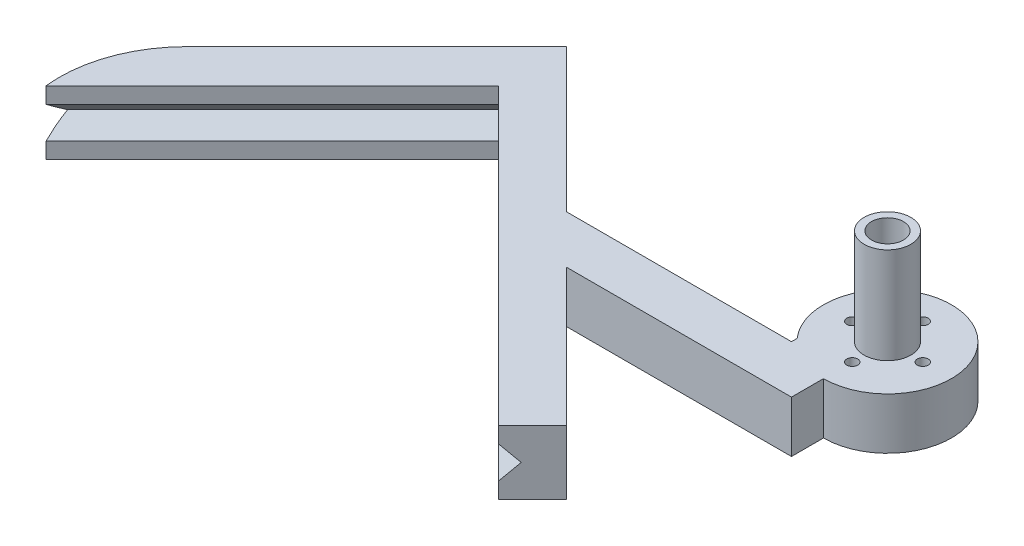
SolidWorks part; units mm, degrees
ref_plane "Front Plane" through (0, 0, 0) normal (0, 0, 1) x (1, 0, 0)
ref_plane "Top Plane" through (0, 0, 0) normal (0, 1, 0) x (1, 0, 0)
ref_plane "Right Plane" through (0, 0, 0) normal (1, 0, 0) x (0, 0, -1)
sketch "Sketch1" plane through (0, 0, 0) normal (0, 1, 0) x (1, 0, 0)
  circle A3 centre (0, -38.254) radius 38.254 construction
  circle A4 centre (0, -40.254) radius 40.254 construction
  circle A5 centre (0, -45.254) radius 45.254 construction
  dimension "D1" = 90.508
  dimension "D2" = 80.508
  dimension "D3" = 76.508
sketch "Sketch3" plane through (0, 0, 0) normal (0, 1, 0) x (1, 0, 0)
  line L8 (58.3717, -39.6268) -> (0, 18.7448)
  line L9 (0, 18.7448) -> (-58.3717, -39.6268)
  line L10 (-58.3717, -39.6268) -> (58.3717, -39.6268) construction
  line L17 (65.1069, -32.8917) -> (37.9076, -5.6924)
  line L18 (0, 32.2152) -> (-65.1069, -32.8917)
  line L19 (-65.1069, -32.8917) -> (-58.3717, -39.6268)
  line L20 (65.1069, -32.8917) -> (58.3717, -39.6268)
  line L23 (82.55, 3.8326) -> (82.55, -5.6924)
  line L26 (65.1069, -32.8917) -> (0, 32.2152) construction
  line L27 (0, 32.2152) -> (-65.1069, -32.8917) construction
  line L28 (28.3826, 3.8326) -> (73.025, 3.8326)
  line L29 (82.55, -5.6924) -> (37.9076, -5.6924)
  line L30 (28.3826, 3.8326) -> (0, 32.2152)
  line L31 (82.55, 3.8326) -> (82.55, 13.3576)
  line L32 (82.55, 13.3576) -> (73.025, 13.3576)
  line L33 (73.025, 13.3576) -> (73.025, 3.8326)
  circle A3 centre (0, -45.254) radius 45.254 construction
  dimension "D1" = 45
  dimension "D2" = 45
  dimension "D3" = 82.55
  dimension "D5" = 9.525
  dimension "D7" = 82.55
  dimension "D6" = 9.525
  dimension "D8" = 52.9844
  dimension "D9" = 9.525
  dimension "D4" = 9.525
extrude "Boss-Extrude1" add sketch "Sketch3" along normal blind 19.05
sketch "Sketch11" plane through (0, 0, 0) normal (0, 1, 0) x (1, 0, 0)
  circle A0 centre (82.55, 13.3576) radius 12.7
  dimension "D1" = 25.4
extrude "Boss-Extrude2" add sketch "Sketch11" along normal blind 19.05
sketch "Sketch14" plane through (0, 0, 0) normal (0, -1, 0) x (1, 0, 0)
  circle A0 centre (89.55, -13.3576) radius 1.077
  circle A2 centre (82.55, -20.3576) radius 1.077
  circle A3 centre (75.55, -13.3576) radius 1.077
  circle A4 centre (82.55, -6.3576) radius 1.077
  circle A5 centre (82.55, -13.3576) radius 12.7 construction
  point P17 (82.55, -13.3576)
  dimension "D2" = 2.154
  dimension "D1" = 7
  dimension "D3" = 4
extrude "Cut-Extrude4" cut sketch "Sketch14" against normal through all
sketch "Sketch16" plane through (0, 0, 0) normal (0, -1, 0) x (1, 0, 0)
  line L2 (37.9076, 5.6924) -> (28.3826, -3.8326)
  line L7 (-65.1069, 32.8917) -> (0, -32.2152)
  line L8 (65.1069, 32.8917) -> (58.3717, 39.6268)
  line L9 (58.3717, 39.6268) -> (0, -18.7448)
  line L10 (0, -18.7448) -> (-58.3717, 39.6268)
  line L20 (-58.3717, 39.6268) -> (-65.1069, 32.8917)
  line L24 (28.3826, -3.8326) -> (73.025, -3.8326)
  line L30 (37.9076, 5.6924) -> (65.1069, 32.8917)
  line L35 (28.3826, -3.8326) -> (73.025, -3.8326)
  line L37 (82.55, 5.6924) -> (37.9076, 5.6924)
  line L38 (82.55, 5.6924) -> (37.9076, 5.6924)
  line L40 (0, -32.2152) -> (28.3826, -3.8326)
  line L47 (82.55, -0.6576) -> (82.55, 5.6924)
  line L48 (82.55, -0.6576) -> (82.55, 5.6924)
  line L49 (73.025, -3.8326) -> (73.025, -4.9573)
  line L50 (73.025, -3.8326) -> (73.025, -4.9573)
  arc A1 (73.025, -4.9573) -> (82.55, -0.6576) centre (82.55, -13.3576) ccw
  arc A6 (73.025, -4.9573) -> (82.55, -0.6576) centre (82.55, -13.3576) ccw
  dimension "D1" = 0
extrude "Cut-Extrude7" cut sketch "Sketch16" against normal blind 8.842
sketch "Sketch17" plane through (0, 19.05, 0) normal (0, 1, 0) x (1, 0, 0)
  line L0 (-65.1069, -32.8917) -> (-51.6365, -19.4213)
  line L1 (0, 32.2152) -> (-65.1069, -32.8917) construction
  line L2 (-51.6365, -19.4213) -> (-44.9013, -26.1565)
  line L3 (-58.3717, -39.6268) -> (0, 18.7448) construction
  line L4 (-44.9013, -26.1565) -> (-58.3717, -39.6268)
  line L5 (-58.3717, -39.6268) -> (-65.1069, -32.8917)
  dimension "D1" = 19.05
extrude "Cut-Extrude8" cut sketch "Sketch17" against normal through all
fillet "Fillet10" radius 25.4 1 edges at (-51.6365, 9.525, 19.4213)
sketch "Sketch18" plane through (0, 19.05, 0) normal (0, 1, 0) x (1, 0, 0)
  circle A0 centre (82.55, 13.3576) radius 3.175
  dimension "D1" = 6.35
extrude "Cut-Extrude9" cut sketch "Sketch18" against normal through all
sketch "Sketch19" plane through (0, 19.05, 0) normal (0, 1, 0) x (1, 0, 0)
  circle A0 centre (82.55, 13.3576) radius 3.175
  circle A1 centre (82.55, 13.3576) radius 4.6355
  dimension "D1" = 9.271
extrude "Boss-Extrude3" add sketch "Sketch19" along normal offset from surface (19.05 mm away) 38.1 up to face at (6.433, 0, 8.7144)
sketch "Sketch20" plane through (0, 0, 0) normal (0, -1, 0) x (1, 0, 0)
  line L5 (0, -18.7448) -> (-44.9013, 26.1565)
  line L6 (-37.6161, 5.4008) -> (0, -32.2152)
  line L7 (0, -32.2152) -> (65.1069, 32.8917)
  line L8 (65.1069, 32.8917) -> (58.3717, 39.6268)
  line L9 (58.3717, 39.6268) -> (0, -18.7448)
  line L10 (0, -18.7448) -> (-44.9013, 26.1565)
  line L11 (-37.6161, 5.4008) -> (0, -32.2152)
  line L12 (0, -32.2152) -> (65.1069, 32.8917)
  line L13 (65.1069, 32.8917) -> (58.3717, 39.6268)
  line L14 (58.3717, 39.6268) -> (0, -18.7448)
  arc A1 (-44.9013, 26.1565) -> (-37.6161, 5.4008) centre (-19.6555, 23.3614) ccw
  arc A3 (-44.9013, 26.1565) -> (-37.6161, 5.4008) centre (-19.6555, 23.3614) ccw
  dimension "D1" = 0
extrude "Cut-Extrude10" cut sketch "Sketch20" against normal blind 6.35
sketch "Sketch21" plane through (48.9993, 0, 48.9993) normal (0.7071, 0, 0.7071) x (0.7071, 0, -0.7071)
  line L0 (13.2546, 15.875) -> (16.4296, 12.7)
  line L1 (13.2546, 19.05) -> (13.2546, 6.35) construction
  line L2 (16.4296, 12.7) -> (13.2546, 9.525)
  line L4 (13.2546, 9.525) -> (13.2546, 15.875)
  point P4 (13.2546, 12.7)
  dimension "D1" = 6.35
extrude "Cut-Extrude11" cut sketch "Sketch21" against normal offset from surface (85.725 mm away) 3.175 up to face at (-22.4506, 12.7, 3.7058) offset beyond the face yes
sketch "Sketch22" plane through (16.1076, 0, -16.1076) normal (0.7071, 0, -0.7071) x (-0.7071, 0, -0.7071)
  line L0 (13.2546, 15.875) -> (13.2546, 9.525)
  line L1 (13.2546, 9.525) -> (16.4296, 12.7)
  line L2 (16.4296, 12.7) -> (13.2546, 15.875)
  line L3 (13.2546, 6.35) -> (13.2546, 19.05) construction
  point P2 (13.2546, 12.7)
  dimension "D1" = 6.35
extrude "Cut-Extrude12" cut sketch "Sketch22" against normal through all from vertex starting at point (0, 12.7, -23.235)
equation "\"tightTol\"= 0.005in"
equation "\"normTol\"= 0.01in"
equation "\"looseTol\"= 0.02in"
equation "\"D1@Sketch1\"=\"looseTol\"+9cm"
equation "\"D2@Sketch1\"=8cm+\"looseTol\""
equation "\"D3@Sketch1\"=7.6cm+\"looseTol\""
equation "\"D2\"= 0.875 - 10.7mm"
equation "\"D1\"= 10.7mm"
equation "\"D1@Boss-Extrude1\"=40mm"
equation "\"D2@Sketch14\"= 1.9mm + \"normTol\""
equation "\"D1@Sketch14\"= 7mm"
equation "\"D19@Boss-Extrude2\"=0.250000-1.5*\"normTol\""
equation "\"D1@Boss-Extrude2\"= 0.75"
equation "\"D1@Cut-Extrude7\" = 15.7mm - 0.25 - \"looseTol\""
equation "\"D1@Sketch19\"=0.375000in-\"normTol\""
equation "\"D8@Sketch3\"=4.95-2.864"
